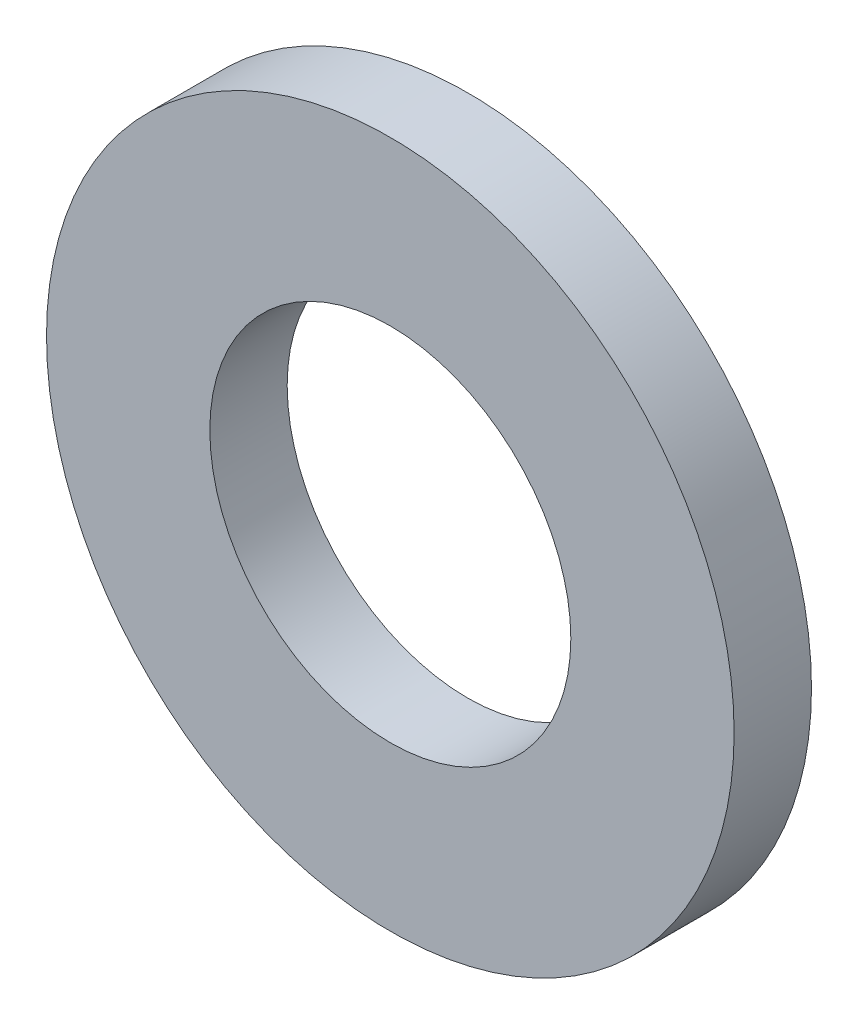
SolidWorks part; units mm, degrees
material "1023 Carbon Steel Sheet (SS)"
ref_plane "Front (1)" through (0, 0, 0) normal (0, 0, 1) x (1, 0, 0)
ref_plane "Top (2)" through (0, 0, 0) normal (0, 1, 0) x (1, 0, 0)
ref_plane "Right (3)" through (0, 0, 0) normal (1, 0, 0) x (0, 0, -1)
ref_axis "X Axis" through (13.5064, 0, 0) along (-1, 0, 0)
ref_axis "Y Axis" through (0, 12.3593, 0) along (0, -1, 0)
ref_axis "Z Axis" through (0, 0, 14.1119) along (0, 0, -1)
sketch "Sketch1" plane through (0, 0, 0) normal (0, 0, 1) x (1, 0, 0)
  circle A0 centre (0, 0) radius 4.2
  circle A1 centre (0, 0) radius 8
  dimension "ID" = 8.4
  dimension "OD" = 16
extrude "Boss-Extrude1" add sketch "Sketch1" along normal blind 1.8
